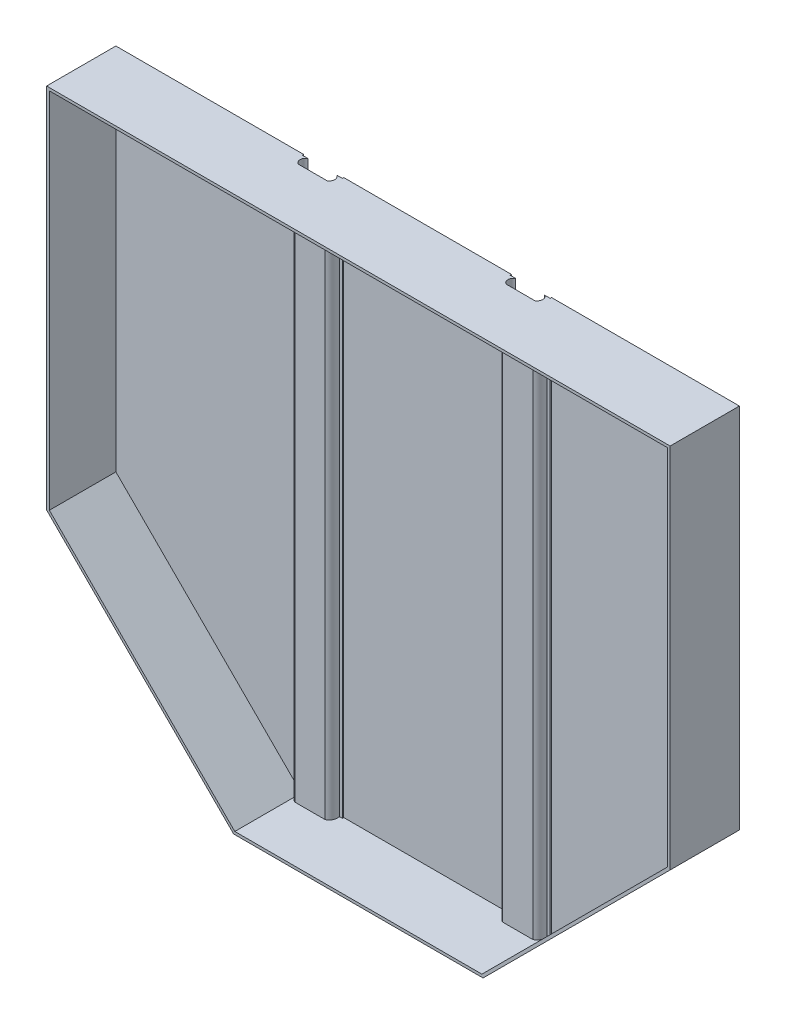
SolidWorks part; units mm, degrees
material "Thornel Mat VMA"
ref_plane "Спереди" through (0, 0, 0) normal (0, 0, 1) x (1, 0, 0)
ref_plane "Сверху" through (0, 0, 0) normal (0, 1, 0) x (1, 0, 0)
ref_plane "Справа" through (0, 0, 0) normal (1, 0, 0) x (0, 0, -1)
other "Configuration Table"
sketch "Sketch2" plane through (0, 0, 0) normal (0, 0, 1) x (1, 0, 0)
  line L0 (0, 391.8357) -> (0, -100.4108) construction
  line L1 (-225, 400) -> (-225, 135)
  line L2 (-225, 135) -> (-90, 0)
  line L3 (-90, 0) -> (90, 0)
  line L4 (90, 0) -> (225, 135)
  line L5 (225, 135) -> (225, 400)
  line L6 (225, 400) -> (-225, 400)
  dimension "D1" = 400
  dimension "D2" = 450
  dimension "D3" = 180
  dimension "D4" = 45
extrude "Boss-Extrude1" add sketch "Sketch2" along normal blind 60
sketch "Sketch4" plane through (0, 0, 0) normal (0, 1, 0) x (1, 0, 0)
  line L0 (-75, 45.8101) -> (-75, -33.9701) construction
  line L1 (-85.4365, -8) -> (-64.5635, -8)
  line L2 (75, 41.1686) -> (75, -38.6116) construction
  line L3 (0, 86.2609) -> (0, -94.2066) construction
  line L4 (-89.4365, 0) -> (-89.4365, -1)
  line L5 (225, 0) -> (-225, 0) construction
  line L6 (-89.4365, -1) -> (-85.4365, -1)
  line L7 (-60.5635, 0) -> (-60.5635, -1)
  line L8 (-60.5635, -1) -> (-64.5635, -1)
  line L9 (64.5635, -8) -> (85.4365, -8)
  line L10 (60.5635, 0) -> (60.5635, -1)
  line L11 (60.5635, -1) -> (64.5635, -1)
  line L12 (89.4365, 0) -> (89.4365, -1)
  line L13 (89.4365, -1) -> (85.4365, -1)
  line L14 (-89.4365, 0) -> (-60.5635, 0)
  line L15 (60.5635, 0) -> (89.4365, 0)
  arc A0 (-85.4365, -1) -> (-85.4365, -8) centre (-83.5, -4.5) ccw
  arc A1 (-64.5635, -1) -> (-64.5635, -8) centre (-66.5, -4.5) cw
  arc A2 (64.5635, -1) -> (64.5635, -8) centre (66.5, -4.5) ccw
  arc A3 (85.4365, -1) -> (85.4365, -8) centre (83.5, -4.5) cw
  dimension "D1" = 8
  dimension "D2" = 7
  dimension "D3" = 25
  dimension "D7" = 8
  dimension "D4" = 75
  dimension "D5" = 1
  dimension "D6" = 4
  dimension "D8" = 7
  dimension "D9" = 25
  dimension "D10" = 1
  dimension "D11" = 4
  dimension "D12" = 75
extrude "Cut-Extrude3" cut sketch "Sketch4" against normal through all and the other way through all contours A3 L13 L12 L15 L10 L11 A2 L9 | A1 L8 L7 L14 L4 L6 A0 L1 region at (-75, 0, 3.9093) region at (75, 0, 3.9093)
shell "Shell1" thickness 2
sketch "Sketch5" plane through (0, 0, 0) normal (0, 1, 0) x (1, 0, 0)
  line L0 (0, 111.147) -> (0, -220.7569) construction
  line L1 (-250, -50) -> (250, -50)
  line L2 (-250, -50) -> (-250, -150)
  line L3 (-250, -150) -> (250, -150)
  line L4 (250, -50) -> (250, -150)
  dimension "D1" = 50
  dimension "D2" = 100
  dimension "D3" = 500
extrude "Cut-Extrude7" cut sketch "Sketch5" along normal through all contours L0 L1 L2 L3 | L1 L0 L3 L4 region at (125, 0, 100) region at (-125, 0, 100)
